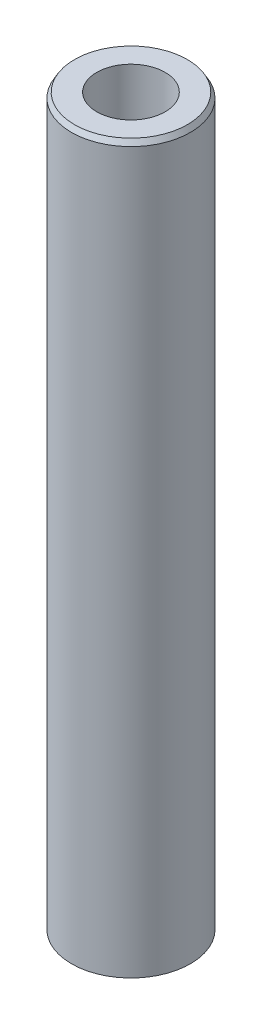
SolidWorks part; units mm, degrees
ref_plane "Front Plane" through (0, 0, 0) normal (0, 0, 1) x (1, 0, 0)
ref_plane "Top Plane" through (0, 0, 0) normal (0, 1, 0) x (1, 0, 0)
ref_plane "Right Plane" through (0, 0, 0) normal (1, 0, 0) x (0, 0, -1)
sketch "Sketch1" plane through (0, 0, 0) normal (0, 1, 0) x (1, 0, 0)
  circle A0 centre (0, 0) radius 15
  dimension "SHAFT_OD" = 30
extrude "Boss-Extrude1" add sketch "Sketch1" along normal blind 183.7214
sketch "Sketch2" plane through (0, 0, 0) normal (0, 1, 0) x (1, 0, 0)
  circle A0 centre (0, 0) radius 8.6288
  dimension "BORE_D" = 17.2577
extrude "Cut-Extrude1" cut sketch "Sketch2" along normal through all
chamfer "Chamfer1" distance 1.3151 angle 30 2 edges at (0, 183.7214, 15) (0, 0, 15) first distance on face at (0, 183.7214, 15) first distance on face at (0, 0, 8.6288)
